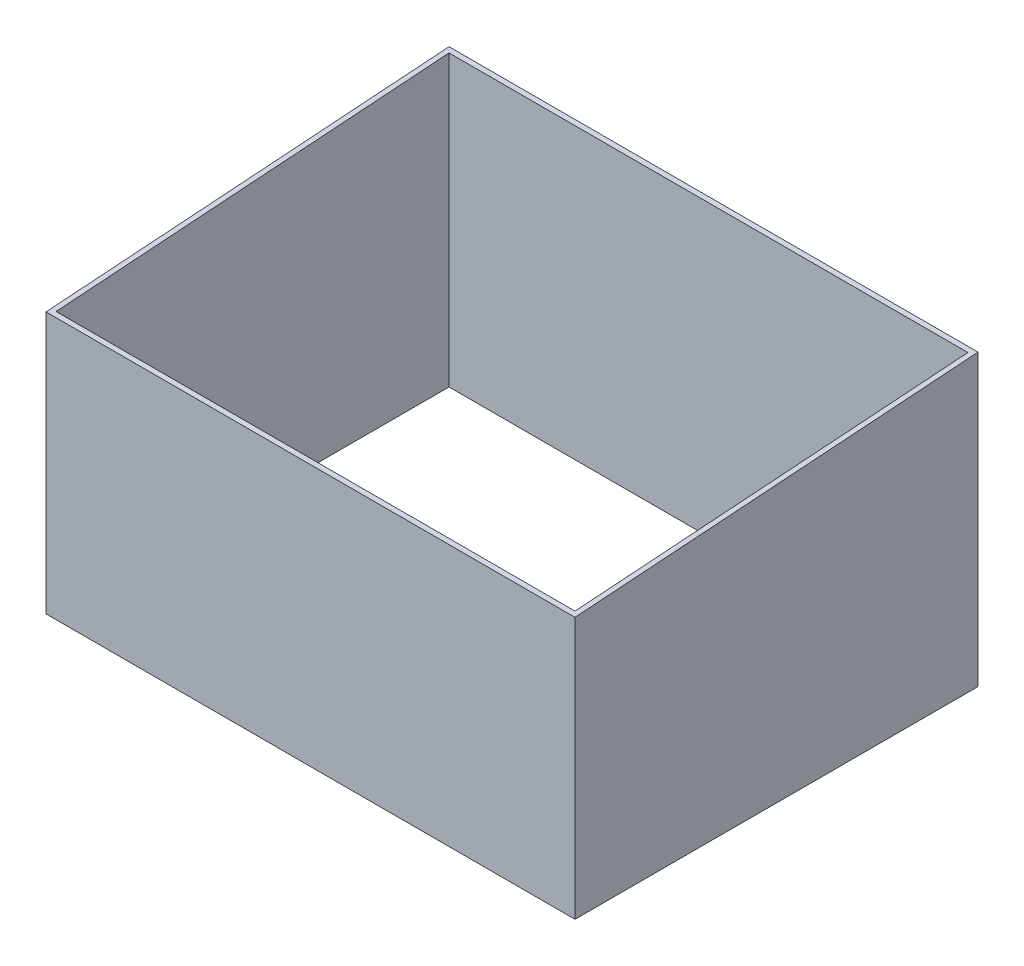
SolidWorks part; units mm, degrees
ref_plane "Спереди" through (0, 0, 0) normal (0, 0, 1) x (1, 0, 0)
ref_plane "Сверху" through (0, 0, 0) normal (0, 1, 0) x (1, 0, 0)
ref_plane "Справа" through (0, 0, 0) normal (1, 0, 0) x (0, 0, -1)
sketch "Эскиз1" plane through (0, 0, 0) normal (0, 1, 0) x (1, 0, 0)
  line L1 (0, 0) -> (4200, 0)
  line L2 (0, 0) -> (0, 3200)
  line L3 (0, 3200) -> (4200, 3200)
  line L4 (4200, 0) -> (4200, 3200)
  dimension "D1" = 3200
  dimension "D2" = 4200
extrude "Вытянуть-Тонкостенный1" add sketch "Эскиз1" along normal blind 2300 thin thin type one direction reverse wall 40
sketch "Эскиз2" plane through (0, 0, 0) normal (-1, 0, 0) x (0, 0, 1)
  line L0 (-3200, 2300) -> (0, 2076.4468)
  line L1 (0, 2300) -> (0, 0) construction
  line L2 (0, 2076.4468) -> (0, 0)
  line L3 (0, 0) -> (-3200, 0)
  line L4 (-3200, 0) -> (-3200, 2300)
extrude "Вырез-Вытянуть1" cut sketch "Эскиз2" against normal through all flip side to cut
